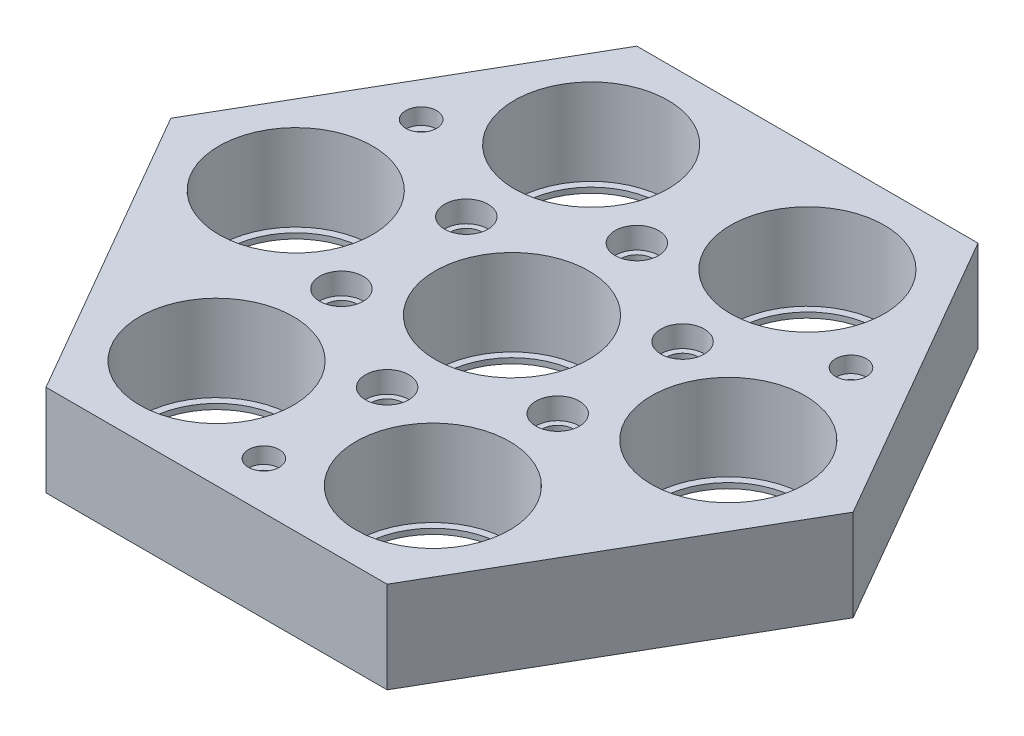
SolidWorks part; units mm, degrees
material "PLA"
ref_plane "Front Plane" through (0, 0, 0) normal (0, 0, 1) x (1, 0, 0)
ref_plane "Top Plane" through (0, 0, 0) normal (0, 1, 0) x (1, 0, 0)
ref_plane "Right Plane" through (0, 0, 0) normal (1, 0, 0) x (0, 0, -1)
sketch "Sketch1" plane through (0, 0, 0) normal (0, 1, 0) x (1, 0, 0)
  line L0 (-23.3, 0) -> (-17, 0) construction
  line L1 (40.3, 0) -> (20.15, 34.9008) construction
  line L2 (20.15, 34.9008) -> (-20.15, 34.9008) construction
  line L3 (-20.15, 34.9008) -> (-40.3, 0) construction
  line L4 (-40.3, 0) -> (-20.15, -34.9008) construction
  line L5 (-20.15, -34.9008) -> (20.15, -34.9008) construction
  line L6 (20.15, -34.9008) -> (40.3, 0) construction
  line L7 (-20.15, 51.9008) -> (-20.15, 55.0508) construction
  line L8 (63.5672, 0) -> (31.7836, 55.0508)
  line L9 (31.7836, 55.0508) -> (-31.7836, 55.0508)
  line L10 (-31.7836, 55.0508) -> (-63.5672, 0)
  line L11 (-63.5672, 0) -> (-31.7836, -55.0508)
  line L12 (-31.7836, -55.0508) -> (31.7836, -55.0508)
  line L13 (31.7836, -55.0508) -> (63.5672, 0)
  line L14 (-20.15, 0) -> (-17, 0)
  circle A0 centre (0, 0) radius 17 construction
  circle A1 centre (0, 0) radius 34.9008 construction
  circle A2 centre (-20.15, 34.9008) radius 17 construction
  circle A3 centre (20.15, 34.9008) radius 17 construction
  circle A4 centre (40.3, 0) radius 17 construction
  circle A5 centre (20.15, -34.9008) radius 17 construction
  circle A6 centre (-20.15, -34.9008) radius 17 construction
  circle A7 centre (-40.3, 0) radius 17 construction
  circle A8 centre (0, 0) radius 55.0508 construction
  circle A9 centre (0, 0) radius 13
  circle A10 centre (-40.3, 0) radius 13
  circle A11 centre (-20.15, 34.9008) radius 13
  circle A12 centre (20.15, 34.9008) radius 13
  circle A13 centre (40.3, 0) radius 13
  circle A14 centre (20.15, -34.9008) radius 13
  circle A15 centre (-20.15, -34.9008) radius 13
  dimension "D1" = 34
  dimension "D3" = 26
  dimension "D2" = 6.3
extrude "Boss-Extrude1" add sketch "Sketch1" along normal blind 1 contours L12 L13 L8 L9 L10 L11 A15 A14 A13 A12 A11 A10 A9 region at (46.2189, 0, 26.6845)
sketch "Sketch2" plane through (0, 1, 0) normal (0, 1, 0) x (1, 0, 0)
  line L0 (-63.5672, 0) -> (-31.7836, 55.0508)
  line L1 (-31.7836, 55.0508) -> (31.7836, 55.0508)
  line L2 (31.7836, 55.0508) -> (63.5672, 0)
  line L3 (63.5672, 0) -> (31.7836, -55.0508)
  line L4 (31.7836, -55.0508) -> (-31.7836, -55.0508)
  line L5 (-31.7836, -55.0508) -> (-63.5672, 0)
  circle A1 centre (-40.3, 0) radius 14.3125
  circle A2 centre (-20.15, 34.9008) radius 14.3125
  circle A3 centre (20.15, 34.9008) radius 14.3125
  circle A4 centre (40.3, 0) radius 14.3125
  circle A5 centre (20.15, -34.9008) radius 14.3125
  circle A6 centre (-20.15, -34.9008) radius 14.3125
  circle A7 centre (0, 0) radius 14.3125
  dimension "D1" = 28.625
extrude "Boss-Extrude2" add sketch "Sketch2" along normal blind 16.05
sketch "Sketch3" plane through (0, 17.05, 0) normal (0, 1, 0) x (1, 0, 0)
  line L0 (-20.15, 34.9008) -> (-40.3, 0) construction
  line L1 (-40.3, 0) -> (0, 0) construction
  line L2 (0, 0) -> (-20.15, 34.9008) construction
  circle A3 centre (-20.15, 11.6336) radius 4.05
  circle A4 centre (0, 23.2672) radius 4.05
  circle A5 centre (20.15, 11.6336) radius 4.05
  circle A6 centre (20.15, -11.6336) radius 4.05
  circle A7 centre (0, -23.2672) radius 4.05
  circle A8 centre (-20.15, -11.6336) radius 4.05
  point P4 (-20.15, 11.6336)
  point P21 (0, 0)
  dimension "D1" = 8.1
  dimension "D2" = 6
extrude "Cut-Extrude1" cut sketch "Sketch3" against normal blind 4
sketch "Sketch5" plane through (0, 17.05, 0) normal (0, 1, 0) x (1, 0, 0)
  line L0 (0, 0) -> (-47.6754, -27.5254) construction
  line L1 (-63.5672, 0) -> (-31.7836, -55.0508) construction
  line L2 (-47.6754, -27.5254) -> (-40.0461, -23.1206)
  line L3 (-40.0461, -23.1206) -> (-40.1429, -14.3116)
  line L4 (-40.3, 0) -> (-40.1429, -14.3116) construction
  circle A0 centre (-40.3, 0) radius 14.3125 construction
  circle A1 centre (-20.15, -34.9008) radius 14.3125 construction
  circle A2 centre (-40.0461, -23.1206) radius 2.875 construction
  circle A3 centre (-40.0461, -23.1206) radius 1.55 construction
  circle A4 centre (-40.0461, 23.1206) radius 1.55
  circle A5 centre (-40.0461, 23.1206) radius 2.875
  circle A6 centre (0, 46.2413) radius 1.55 construction
  circle A7 centre (0, 46.2413) radius 2.875 construction
  circle A8 centre (40.0461, 23.1206) radius 1.55
  circle A9 centre (40.0461, 23.1206) radius 2.875
  circle A10 centre (40.0461, -23.1206) radius 1.55 construction
  circle A11 centre (40.0461, -23.1206) radius 2.875 construction
  circle A12 centre (0, -46.2413) radius 1.55
  circle A13 centre (0, -46.2413) radius 2.875
  point P32 (0, 0)
  dimension "D1" = 5.75
  dimension "D2" = 3.1
  dimension "D3" = 6
extrude "Cut-Extrude3" cut sketch "Sketch5" against normal through all contours A4 | A8 | A12
extrude "Cut-Extrude4" cut sketch "Sketch5<3>" against normal blind 3 contours A13 | A5 | A9
sketch "Sketch5<3>" plane through (0, 17.05, 0) normal (0, 1, 0) x (1, 0, 0) same geometry as "Sketch5"
sketch "Sketch6" plane through (0, 13.05, 0) normal (0, 1, 0) x (1, 0, 0)
  circle A0 centre (-20.15, -11.6336) radius 3
  circle A1 centre (-20.15, 11.6336) radius 3
  circle A2 centre (0, 23.2672) radius 3
  circle A3 centre (20.15, 11.6336) radius 3
  circle A4 centre (20.15, -11.6336) radius 3
  circle A5 centre (0, -23.2672) radius 3
  point P15 (0, 0)
  dimension "D1" = 6
  dimension "D2" = 6
extrude "Cut-Extrude5" cut sketch "Sketch6" against normal through all
